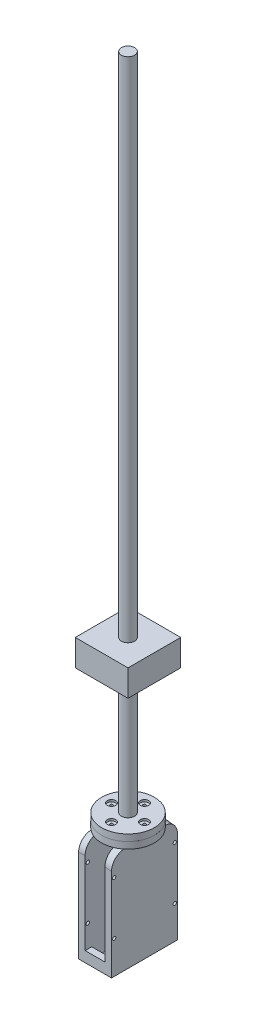
SolidWorks part; units mm, degrees
ref_plane "Front Plane" through (0, 0, 0) normal (0, 0, 1) x (1, 0, 0)
ref_plane "Top Plane" through (0, 0, 0) normal (0, 1, 0) x (1, 0, 0)
ref_plane "Right Plane" through (0, 0, 0) normal (1, 0, 0) x (0, 0, -1)
sketch "Sketch1" plane through (0, 0, 0) normal (0, 1, 0) x (1, 0, 0)
  circle A0 centre (0, 0) radius 20
  dimension "D1" = 40
extrude "Boss-Extrude1" add sketch "Sketch1" along normal blind 5
sketch "Sketch3" plane through (0, 5, 0) normal (0, 1, 0) x (1, 0, 0)
  circle A0 centre (0, 0) radius 5
  dimension "D1" = 10
extrude "Cut-Extrude1" cut sketch "Sketch3" against normal up to next
hole_wizard "CBORE for M2 Hex Head Machine Screw1" positions "Sketch5" profile "Sketch6" counterbore size "M2" standard "ANSI Metric" end condition through all
sketch "Sketch5" plane through (0, 5, 0) normal (0, 1, 0) x (1, 0, 0)
  line L0 (-5, 20.5281) -> (-5, -22.8294) construction
  line L2 (-20, 15.296) -> (-20, -16.8443) construction
  line L4 (-20, 0) -> (-12.5, 0) construction
  line L5 (-12.5, 0) -> (-5, 0) construction
  circle A1 centre (0, 0) radius 5 construction
  circle A2 centre (0, 0) radius 20 construction
  point P0 (-12.5, 0)
sketch "Sketch6" plane through (-12.5, 5, 0) normal (1, 0, 0) x (0, 0, 1)
  line L0 (0, 0) -> (0, 5)
  line L1 (0, 5) -> (1.1, 5)
  line L3 (1.1, 5) -> (1.1, 1.6)
  line L4 (1.1, 1.6) -> (3.19, 1.6)
  line L5 (3.19, 1.6) -> (3.19, 0)
  line L7 (3.19, 0) -> (0, 0)
  line L11 (0, -6.35) -> (0, 107.95) construction
  dimension "Thru Hole Dia." = 2.2
  dimension "Thru Hole Depth" = 5
  dimension "C'Bore Dia." = 6.38
  dimension "C'Bore Depth" = 1.6
pattern_circular "CirPattern1" count 4 every 90 about axis through (0, 5, 0) along (0, 1, 0) of "CBORE for M2 Hex Head Machine Screw1"
sketch "Sketch7" plane through (0, 0, 0) normal (0, -1, 0) x (1, 0, 0)
  circle A0 centre (-12.5, 0) radius 1.1 construction
  circle A1 centre (0, -12.5) radius 1.1 construction
  circle A2 centre (12.5, 0) radius 1.1 construction
  circle A3 centre (0, 12.5) radius 1.1 construction
  circle A4 centre (0, 0) radius 20 construction
  circle A5 centre (0, 0) radius 5 construction
  circle A6 centre (-12.5, 0) radius 1.1
  circle A7 centre (0, -12.5) radius 1.1
  circle A8 centre (12.5, 0) radius 1.1
  circle A9 centre (0, 12.5) radius 1.1
  circle A10 centre (0, 0) radius 20
  circle A11 centre (0, 0) radius 5
extrude "Boss-Extrude2" add sketch "Sketch7" along normal blind 5 separate body
sketch "Sketch8" plane through (0, -5, 0) normal (0, -1, 0) x (1, 0, 0)
  line L1 (-12.5, 25) -> (-7.5, 25)
  line L2 (-12.5, 25) -> (-12.5, -25)
  line L3 (-12.5, -25) -> (-7.5, -25)
  line L4 (-7.5, 25) -> (-7.5, -25)
  line L5 (7.5, 25) -> (12.5, 25)
  line L6 (7.5, 25) -> (7.5, -25)
  line L7 (7.5, -25) -> (12.5, -25)
  line L8 (12.5, 25) -> (12.5, -25)
  point P8 (-7.5, 0)
  point P9 (7.5, 0)
  dimension "D1" = 15
  dimension "D2" = 7.5
  dimension "D3" = 5
  dimension "D4" = 50
extrude "Boss-Extrude3" add sketch "Sketch8" along normal blind 80
sketch "Sketch9" plane through (12.5, 0, 0) normal (1, 0, 0) x (0, 0, -1)
  line L0 (-25, -85) -> (-25, -5) construction
  line L2 (50, -5) -> (-25, -5) construction
  line L3 (-25, -40) -> (25, -40) construction
  line L4 (25, -85) -> (25, -5) construction
  line L6 (0, 0) -> (0, -85) construction
  circle A0 centre (-23, -20) radius 1.25
  circle A1 centre (23, -20) radius 1.25
  circle A2 centre (23, -60) radius 1.25
  circle A3 centre (-23, -60) radius 1.25
  dimension "D1" = 2.5
  dimension "D2" = 2.5
  dimension "D4" = 2
  dimension "D5" = 15
  dimension "D6" = 35
extrude "Cut-Extrude2" cut sketch "Sketch9" against normal through all
fillet "Fillet1" radius 10 4 edges at (-10, -5, -25) (10, -5, -25) (10, -5, 25) (-10, -5, 25)
sketch "Sketch11" plane through (7.5, 0, 0) normal (-1, 0, 0) x (0, 0, 1)
  line L0 (25, -85) -> (-25, -85) construction
  line L1 (25, -85) -> (20, -85)
  line L2 (25, -85) -> (25, -77)
  line L3 (25, -77) -> (20, -77)
  line L4 (20, -85) -> (20, -77)
  line L5 (25, -85) -> (25, -14.9887) construction
  line L6 (0, 13.1067) -> (0, -94.2059) construction
  line L7 (-20, -85) -> (-20, -77)
  line L8 (-25, -85) -> (-20, -85)
  line L9 (-25, -85) -> (-25, -77)
  line L10 (-25, -77) -> (-20, -77)
  dimension "D1" = 8
  dimension "D2" = 5
extrude "Boss-Extrude4" add sketch "Sketch11" along normal up to next
sketch "Sketch12" plane through (0, 5, 0) normal (0, 1, 0) x (1, 0, 0)
  circle A0 centre (0, 0) radius 5
  dimension "D1" = 10
extrude "Boss-Extrude5" add sketch "Sketch12" along normal blind 500 and the other way blind 10 separate body
sketch "Sketch14" plane through (0, 0, 0) normal (0, 0, 1) x (1, 0, 0)
  line L0 (-20, 100) -> (20, 100)
  line L5 (-20, 100) -> (-20, 120)
  line L6 (-20, 120) -> (20, 120)
  line L7 (20, 100) -> (20, 120)
  line L10 (0, -28.1389) -> (0, 28.1389) construction
  line L12 (22, 0) -> (-22, 0) construction
  point P10 (-14.5842, 512.1711)
  dimension "D1" = 40
  dimension "D2" = 20
  dimension "D3" = 20
  dimension "D4" = 100
extrude "Boss-Extrude6" add sketch "Sketch14" along normal mid plane 40 separate body
sketch "Sketch16" plane through (0, 100, 0) normal (0, -1, 0) x (1, 0, 0)
  line L0 (0, -28.1389) -> (0, 28.1389) construction
  line L1 (7.5, 4.3301) -> (0, 8.6603)
  line L2 (0, 8.6603) -> (-7.5, 4.3301)
  line L3 (-7.5, 4.3301) -> (-7.5, -4.3301)
  line L4 (-7.5, -4.3301) -> (0, -8.6603)
  line L5 (0, -8.6603) -> (7.5, -4.3301)
  line L6 (7.5, -4.3301) -> (7.5, 4.3301)
  circle A0 centre (0, 0) radius 7.5 construction
  point P1 (0, 0)
  point P12 (9.9373, -5.7373)
  point P13 (7.6766, -4.4321)
  dimension "D1" = 15
extrude "Boss-Extrude7" add sketch "Sketch16" along normal blind 10
